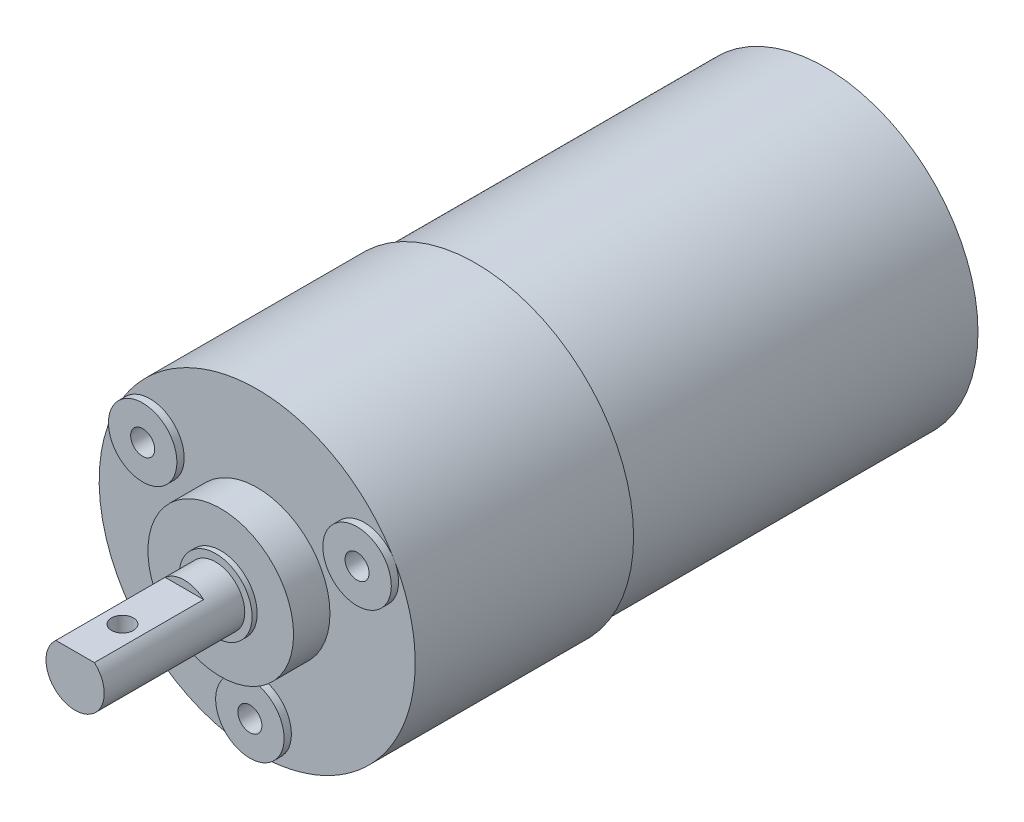
SolidWorks part; units mm, degrees
ref_plane "Front Plane" through (0, 0, 0) normal (0, 0, 1) x (1, 0, 0)
ref_plane "Top Plane" through (0, 0, 0) normal (0, 1, 0) x (1, 0, 0)
ref_plane "Right Plane" through (0, 0, 0) normal (1, 0, 0) x (0, 0, -1)
sketch "Sketch1" plane through (0, 0, 0) normal (0, 0, 1) x (1, 0, 0)
  circle A0 centre (0, 0) radius 21
  dimension "D1" = 42
extrude "Boss-Extrude1" add sketch "Sketch1" along normal blind 48
sketch "Sketch2" plane through (0, 0, 48) normal (0, 0, 1) x (1, 0, 0)
  circle A0 centre (0, 0) radius 21.7
  dimension "D1" = 43.4
extrude "Boss-Extrude2" add sketch "Sketch2" along normal blind 30
sketch "Sketch3" plane through (0, 0, 78) normal (0, 0, 1) x (1, 0, 0)
  circle A0 centre (0, 0) radius 17 construction
  circle A1 centre (0, -17) radius 4.7
  circle A2 centre (0, 0) radius 21.7 construction
  circle A3 centre (-14.7224, 8.5) radius 4.7
  circle A4 centre (14.7224, 8.5) radius 4.7
  circle A5 centre (0, 0) radius 10
  point P14 (0, 0)
  dimension "D1" = 34
  dimension "D2" = 3
  dimension "D3" = 20
extrude "Boss-Extrude3" add sketch "Sketch3" along normal blind 1 contours A3 | A4 | A1 region at (0, -17, 78) region at (-14.7224, 8.5, 78) region at (14.7224, 8.5, 78)
extrude "Boss-Extrude4" add sketch "Sketch3<3>" along normal blind 5 contours A5
sketch "Sketch3<3>" plane through (0, 0, 78) normal (0, 0, 1) x (1, 0, 0) same geometry as "Sketch3"
sketch "Sketch4" plane through (0, 0, 83) normal (0, 0, 1) x (1, 0, 0)
  circle A0 centre (0, 0) radius 4
  dimension "D1" = 8
extrude "Boss-Extrude5" add sketch "Sketch4" along normal blind 20
sketch "Sketch5" plane through (0, 0, 103) normal (0, 0, 1) x (1, 0, 0)
  line L0 (0, 4) -> (0, 3) construction
  line L1 (-2.6458, 3) -> (2.6458, 3)
  circle A0 centre (0, 0) radius 4 construction
  point P8 (0, 3)
  dimension "D1" = 1
extrude "Cut-Extrude1" cut sketch "Sketch5" against normal blind 15 and the other way through all
sketch "Sketch6" plane through (0, 3, 0) normal (0, 1, 0) x (1, 0, 0)
  line L0 (0, -103) -> (0, -96.5) construction
  line L1 (-2.6458, -103) -> (2.6458, -103) construction
  circle A0 centre (0, -96.5) radius 1.5
  dimension "D2" = 3
  dimension "D1" = 6.5
extrude "Cut-Extrude2" cut sketch "Sketch6" against normal blind 15
hole_wizard "M4x0.7 Tapped Hole2" positions "3DSketch2" profile "Sketch8" tap size "M4x0.7" standard "ANSI Metric"
sketch3d "3DSketch2"
  line L0 (0, -17, 79) -> (0, -17, 78) construction
  line L1 (14.7224, 8.5, 79) -> (14.7224, 8.5, 78) construction
  line L2 (-14.7224, 8.5, 79) -> (-14.7224, 8.5, 78) construction
  point P0 (0, -17, 79)
  point P4 (14.7224, 8.5, 79)
  point P8 (-14.7224, 8.5, 79)
sketch "Sketch8" plane through (0, -17, 79) normal (1, 0, 0) x (0, -1, 0)
  line L0 (0, 0) -> (0, 11.0914)
  line L1 (0, 11.0914) -> (1.65, 10.1)
  line L2 (1.65, 10.1) -> (1.65, 0)
  line L5 (1.65, 0) -> (0, 0)
  line L10 (0, 11.0914) -> (-1.65, 10.1) construction
  line L11 (0, -6.35) -> (0, 107.95) construction
  dimension "Tap Drill Dia." = 3.3
  dimension "Tap Drill Depth" = 10.1
  dimension "Drill Angle" = 118
cosmetic thread "Hole Thread1" parameters "D1"=8, "D2"=4
cosmetic thread "Hole Thread2" parameters "D1"=8, "D2"=4
cosmetic thread "Hole Thread3" parameters "D1"=8, "D2"=4
sketch "Sketch9" plane through (0, 0, 83) normal (0, 0, 1) x (1, 0, 0)
  circle A0 centre (0, 0) radius 4 construction
  circle A1 centre (0, 0) radius 4
  circle A2 centre (0, 0) radius 5
  dimension "D1" = 1
extrude "Boss-Extrude6" add sketch "Sketch9" along normal blind 0.7
